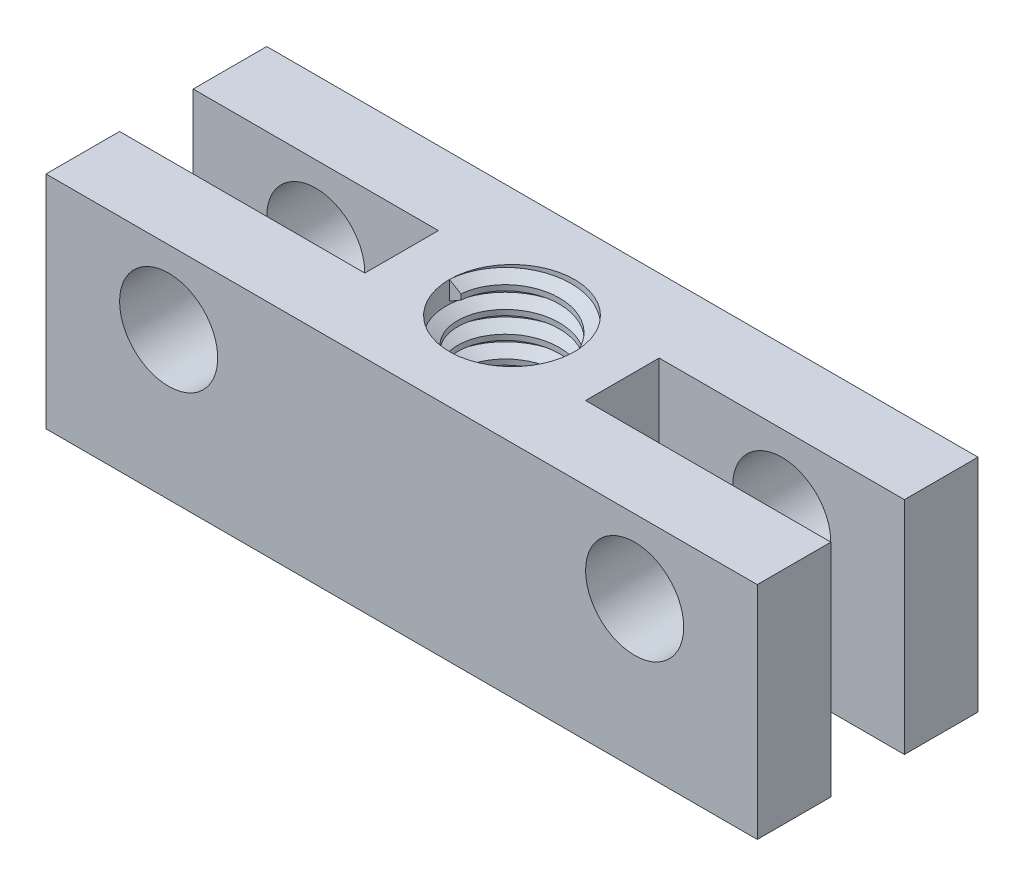
SolidWorks part; units mm, degrees
ref_plane "Front Plane" through (0, 0, 0) normal (0, 0, 1) x (1, 0, 0)
ref_plane "Top Plane" through (0, 0, 0) normal (0, 1, 0) x (1, 0, 0)
ref_plane "Right Plane" through (0, 0, 0) normal (1, 0, 0) x (0, 0, -1)
sketch "Sketch1" plane through (0, 0, 0) normal (0, 1, 0) x (1, 0, 0)
  line L1 (-13.5, 1.5) -> (4.5, 1.5)
  line L3 (-13.5, -1.5) -> (-11.9429, -1.5)
  line L4 (4.5, 1.5) -> (4.5, -4.5)
  line L5 (-13.5, -4.5) -> (4.5, -4.5)
  line L6 (-33.5, -4.5) -> (-33.5, -10.5)
  line L7 (-33.5, 1.5) -> (24.5, 1.5)
  line L9 (-33.5, 7.5) -> (24.5, 7.5)
  line L10 (24.5, 1.5) -> (24.5, 7.5)
  line L12 (-13.5, 1.5) -> (-13.5, -4.5)
  line L13 (-33.5, 1.5) -> (-33.5, 7.5)
  line L14 (-33.5, -4.5) -> (24.5, -4.5)
  line L15 (24.5, -4.5) -> (24.5, -10.5)
  line L16 (-33.5, -10.5) -> (24.5, -10.5)
  point P0 (0, 0)
  dimension "D1" = 9
  dimension "D2" = 6
  dimension "D3" = 20
extrude "Boss-Extrude1" add sketch "Sketch1" along normal blind 18 contours L6 L16 L15 L14 L5 | L13 L7 L1 L10 L9 | L1 L12 L5 L4 region at (-4.5, 0, -4.5) region at (-4.5, 0, 1.5) region at (-4.5, 0, 7.5)
hole_wizard "M12 Tapped Hole1" positions "3DSketch1" profile "Sketch2" tap size "M12" standard "ISO" end condition through all
sketch3d "3DSketch1"
  line L0 (-4.5, 18, -7.5) -> (-4.5, 18, 9.434) construction
  line L1 (-33.5, 18, -7.5) -> (24.5, 18, -7.5) construction
  line L3 (-13.5, 18, 1.5) -> (2.422, 18, 1.5) construction
  line L4 (-13.5, 18, -1.5) -> (-13.5, 18, 4.5) construction
  point P0 (-4.5, 18, 1.5)
sketch "Sketch2" plane through (-4.5, 18, 1.5) normal (1, 0, 0) x (0, 0, 1)
  line L0 (0, 0) -> (0, 18)
  line L1 (0, 18) -> (5.1, 18)
  line L2 (5.1, 18) -> (5.1, 0)
  line L5 (5.1, 0) -> (0, 0)
  line L11 (0, -6.35) -> (0, 107.95) construction
  dimension "Thru Tap Drill Dia." = 10.2
  dimension "Thru Tap Drill Depth" = 18
cosmetic thread "Hole Thread1" parameters "D2"=12
thread "Thread1" pitch 1.75 method extrude profile "Thread Profile1" start angle 0, offset 0, length 18, pitch 1.75, diameter 10.2
ref_plane "Plane1" through (-9.6, 18, 1.5) normal (0, 0, 1) x (-1, 0, 0)
sketch "Thread Profile1" plane through (-9.6, 18, 1.5) normal (0, 0, 1) x (-1, 0, 0)
  line L0 (0, 0) -> (0, 1.75) construction
  line L11 (0, 0) -> (0, 1.5312)
  line L12 (0, 1.5312) -> (-0.9472, 0.9844)
  line L13 (-0.9472, 0.9844) -> (-0.9472, 0.5469)
  line L15 (-0.9472, 0.5469) -> (0, 0)
  line L17 (-0.9472, 0.7656) -> (0, 0.7656) construction
  point P2 (0, 0)
  dimension "Pitch" = 1.75
  dimension "Profile_Angle" = 60
  dimension "Profile_Land" = 0.4375
  dimension "Profile_Height" = 0.9472
sketch "Sketch6" plane through (0, 0, -7.5) normal (0, 0, -1) x (-1, 0, 0)
  line L0 (33.5, 0) -> (-24.5, 0) construction
  line L1 (33.5, 18) -> (-24.5, 18) construction
  line L2 (4.5, 18) -> (4.5, -5.0449) construction
  circle A0 centre (23.5, 12) radius 4
  circle A1 centre (-14.5, 12) radius 4
  point P6 (4.5, 18)
  dimension "D1" = 8
  dimension "D2" = 12
  dimension "D3" = 19
extrude "Cut-Extrude1" cut sketch "Sketch6" against normal through all
